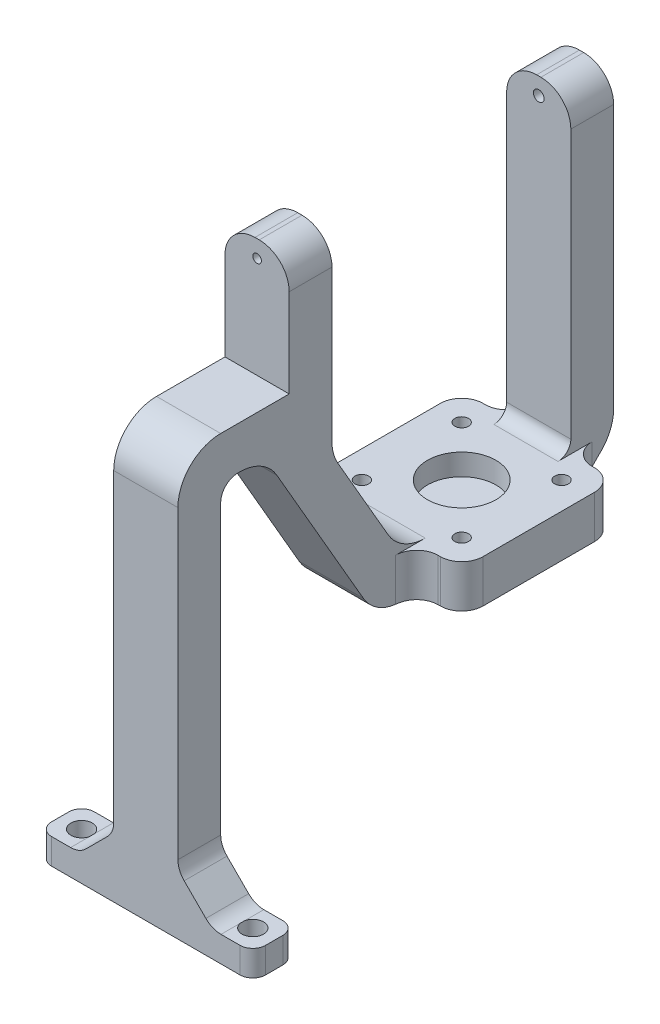
SolidWorks part; units mm, degrees
ref_plane "Front Plane" through (0, 0, 0) normal (0, 0, 1) x (1, 0, 0)
ref_plane "Top Plane" through (0, 0, 0) normal (0, 1, 0) x (1, 0, 0)
ref_plane "Right Plane" through (0, 0, 0) normal (1, 0, 0) x (0, 0, -1)
sketch "Sketch1" plane through (0, 0, 0) normal (0, 0, 1) x (1, 0, 0)
  line L11 (-20, 396.658) -> (20, 396.658)
  line L17 (-20, 396.658) -> (-20, 446.658)
  line L18 (-20, 446.658) -> (20, 446.658)
  line L19 (20, 396.658) -> (20, 446.658)
extrude "Boss-Extrude1" add sketch "Sketch1" along normal blind 5
sketch "Sketch5" plane through (0, 0, 0) normal (1, 0, 0) x (0, 0, -1)
  line L2 (-10, 370) -> (-10, 467.3207)
  line L3 (-10, 467.3207) -> (16, 467.3207)
  line L4 (16, 467.3207) -> (42.0195, 422.2536)
  line L5 (42.0195, 422.2536) -> (76.246, 422.2536)
  line L6 (76.246, 422.2536) -> (76.246, 412.2536)
  line L7 (76.246, 412.2536) -> (36.246, 412.2536)
  line L8 (36.246, 412.2536) -> (10.2265, 457.3207)
  line L9 (10.2265, 457.3207) -> (0, 457.3207)
  line L12 (-10, 370) -> (0, 370)
  line L13 (0, 370) -> (0, 457.3207)
extrude "Boss-Extrude2" add sketch "Sketch5" along normal mid plane 15
fillet "Fillet3" radius 10 4 edges at (0, 422.2536, -42.0195) (0, 412.2536, -36.246) (0, 457.3207, -10.2265) (0, 467.3207, 10)
sketch "Sketch6" plane through (0, 0, 0) normal (1, 0, 0) x (0, 0, -1)
  line L0 (42.0195, 412.2536) -> (76.246, 412.2536) construction
  line L1 (81.8142, 422.2536) -> (45.8142, 422.2536)
  line L2 (81.8142, 422.2536) -> (81.8142, 412.2536)
  line L3 (81.8142, 412.2536) -> (45.8142, 412.2536)
  line L4 (45.8142, 422.2536) -> (45.8142, 412.2536)
  line L5 (76.246, 422.2536) -> (47.793, 422.2536) construction
  dimension "D1" = 36
  dimension "D2" = 0
extrude "Boss-Extrude3" add sketch "Sketch6" along normal mid plane 36
sketch "Sketch7" plane through (0, 422.2536, 0) normal (0, 1, 0) x (1, 0, 0)
  line L0 (-18, 63.8142) -> (18, 63.8142) construction
  line L1 (-18, 81.8142) -> (-18, 45.8142) construction
  line L3 (0, 63.8142) -> (0, 81.8142) construction
  line L4 (18, 81.8142) -> (-18, 81.8142) construction
  circle A1 centre (0, 63.8142) radius 8
extrude "Cut-Extrude3" cut sketch "Sketch7" against normal blind 5
fillet "Fillet5" radius 5 6 edges at (-18, 417.2536, -81.8142) (18, 417.2536, -81.8142) (-18, 417.2536, -45.8142) (18, 417.2536, -45.8142) (-7.5, 417.2536, -45.8142) (7.5, 417.2536, -45.8142)
sketch "Sketch8" plane through (0, 422.2536, 0) normal (0, 1, 0) x (1, 0, 0)
  circle A0 centre (11.6673, 52.147) radius 1.6
  circle A1 centre (-11.6673, 52.147) radius 1.6
  circle A2 centre (-11.6673, 75.4815) radius 1.6
  circle A3 centre (11.6673, 75.4815) radius 1.6
extrude "Cut-Extrude4" cut sketch "Sketch8" against normal through all
fillet "Fillet6" radius 3 4 edges at (-20, 396.658, 2.5) (-20, 446.658, 2.5) (20, 396.658, 2.5) (20, 446.658, 2.5)
sketch "Sketch9" plane through (7.5, 0, 0) normal (1, 0, 0) x (0, 0, -1)
  line L0 (26, 450.0002) -> (26, 495.0002)
  line L1 (39.1328, 427.2536) -> (16, 467.3207) construction
  line L2 (16, 467.3207) -> (16, 495.0002)
  line L3 (16, 495.0002) -> (26, 495.0002)
  line L4 (16, 467.3207) -> (26, 450.0002)
  dimension "D1" = 10
  dimension "D2" = 45
extrude "Boss-Extrude4" add sketch "Sketch9" against normal up to surface (15 mm away) up to face at (-7.5, 428.7111, -11.931)
sketch "Sketch10" plane through (0, 0, -16) normal (0, 0, 1) x (1, 0, 0)
  line L0 (0, 495.0002) -> (0, 467.3207) construction
  line L1 (-7.5, 495.0002) -> (7.5, 495.0002) construction
  line L2 (-7.5, 467.3207) -> (7.5, 467.3207) construction
  circle A0 centre (0, 491.0002) radius 1
extrude "Cut-Extrude5" cut sketch "Sketch10" against normal through all
fillet "Fillet8" radius 10 1 edges at (0, 450.0002, -26)
fillet "Fillet9" radius 7 2 edges at (-7.5, 495.0002, -21) (7.5, 495.0002, -21)
sketch "Sketch12" plane through (0, 0, 5) normal (0, 0, 1) x (1, 0, 0)
  line L4 (7.5, 396.658) -> (17, 396.658)
  line L5 (20, 399.658) -> (20, 443.658)
  line L6 (17, 446.658) -> (7.5, 446.658)
  line L7 (7.5, 446.658) -> (7.5, 396.658)
  line L8 (7.5, 396.658) -> (17, 396.658)
  line L9 (20, 399.658) -> (20, 443.658)
  line L10 (17, 446.658) -> (7.5, 446.658)
  line L11 (7.5, 446.658) -> (7.5, 396.658)
  line L12 (-20, 443.658) -> (-20, 399.658)
  line L13 (-17, 396.658) -> (-7.5, 396.658)
  line L14 (-7.5, 396.658) -> (-7.5, 446.658)
  line L15 (-7.5, 446.658) -> (-17, 446.658)
  line L16 (-20, 443.658) -> (-20, 399.658)
  line L17 (-17, 396.658) -> (-7.5, 396.658)
  line L18 (-7.5, 396.658) -> (-7.5, 446.658)
  line L19 (-7.5, 446.658) -> (-17, 446.658)
  arc A2 (17, 396.658) -> (20, 399.658) centre (17, 399.658) ccw
  arc A3 (20, 443.658) -> (17, 446.658) centre (17, 443.658) ccw
  arc A4 (17, 396.658) -> (20, 399.658) centre (17, 399.658) ccw
  arc A5 (20, 443.658) -> (17, 446.658) centre (17, 443.658) ccw
  arc A6 (-20, 399.658) -> (-17, 396.658) centre (-17, 399.658) ccw
  arc A7 (-17, 446.658) -> (-20, 443.658) centre (-17, 443.658) ccw
  arc A8 (-20, 399.658) -> (-17, 396.658) centre (-17, 399.658) ccw
  arc A9 (-17, 446.658) -> (-20, 443.658) centre (-17, 443.658) ccw
  dimension "D1" = 0
  dimension "D2" = 0
extrude "Cut-Extrude7" cut sketch "Sketch12" against normal up to surface (5 mm away) up to face at (0, 419.6586, 0)
fillet "Fillet10" radius 4 1 edges at (0, 457.3207, 0)
sketch "Sketch13" plane through (0, 0, 0) normal (1, 0, 0) x (0, 0, -1)
  line L0 (0, 370) -> (0, 453.3207) construction
  line L1 (-10, 370) -> (0, 370)
  line L2 (-10, 370) -> (-10, 376)
  line L3 (-10, 376) -> (0, 376)
  line L4 (0, 370) -> (0, 376)
  dimension "D1" = 6
extrude "Boss-Extrude5" add sketch "Sketch13" along normal mid plane 50
chamfer "Chamfer1" distance 8 angle 45 2 edges at (-7.5, 376, 5) (7.5, 376, 5)
fillet "Fillet11" radius 5 4 edges at (-15.5, 376, 5) (-7.5, 384, 5) (7.5, 384, 5) (15.5, 376, 5)
fillet "Fillet12" radius 3 4 edges at (-25, 373, 0) (-25, 373, 10) (25, 373, 0) (25, 373, 10)
sketch "Sketch18" plane through (0, 0, -81.8142) normal (0, 0, -1) x (-1, 0, 0)
  line L0 (7.5, 427.2536) -> (7.5, 447.6797) construction
  line L1 (7.5, 412.2536) -> (7.5, 488.0002)
  line L2 (-7.5, 427.2536) -> (-7.5, 447.6797) construction
  line L3 (-7.5, 412.2536) -> (-7.5, 488.0002)
  line L4 (0.5, 495.0002) -> (-0.5, 495.0002) construction
  line L5 (0.5, 495.0002) -> (-0.5, 495.0002)
  line L6 (-13, 412.2536) -> (13, 412.2536) construction
  line L7 (-7.5, 412.2536) -> (7.5, 412.2536)
  arc A0 (-0.5, 495.0002) -> (-7.5, 488.0002) centre (-0.5, 488.0002) ccw construction
  arc A1 (7.5, 488.0002) -> (0.5, 495.0002) centre (0.5, 488.0002) ccw construction
  arc A2 (-0.5, 495.0002) -> (-7.5, 488.0002) centre (-0.5, 488.0002) ccw
  arc A3 (7.5, 488.0002) -> (0.5, 495.0002) centre (0.5, 488.0002) ccw
extrude "Boss-Extrude7" add sketch "Sketch18" along normal blind 10
chamfer "Chamfer2" distance 10 angle 45 1 edges at (0, 412.2536, -91.8142)
fillet "Fillet15" radius 10 1 edges at (0, 422.2536, -91.8142)
fillet "Fillet16" radius 3 1 edges at (0, 422.2536, -81.8142)
fillet "Fillet17" radius 5 2 edges at (-7.5, 417.2536, -81.8142) (7.5, 417.2536, -81.8142)
sketch "Sketch19" plane through (0, 0, -91.8142) normal (0, 0, -1) x (-1, 0, 0)
  circle A0 centre (0, 491.0002) radius 1.25
extrude "Cut-Extrude8" cut sketch "Sketch19" against normal up to surface (10 mm away) up to face at (0, 469.9013, -81.8142)
sketch "Sketch20" plane through (0, 376, 0) normal (0, 1, 0) x (1, 0, 0)
  line L0 (25, -5) -> (20, -5) construction
  line L1 (25, -3) -> (25, -7) construction
  line L2 (-25, -3) -> (-25, -7) construction
  line L3 (20, -10) -> (20, 0) construction
  line L4 (22, -10) -> (17.5711, -10) construction
  line L5 (22, 0) -> (17.5711, 0) construction
  line L6 (-20, -10) -> (-20, 0) construction
  line L7 (-17.5711, -10) -> (-22, -10) construction
  line L8 (-17.5711, 0) -> (-22, 0) construction
  line L9 (-20, -5) -> (-25, -5) construction
  circle A0 centre (-20, -5) radius 2.5
  circle A1 centre (20, -5) radius 2.5
extrude "Cut-Extrude9" cut sketch "Sketch20" against normal through all
